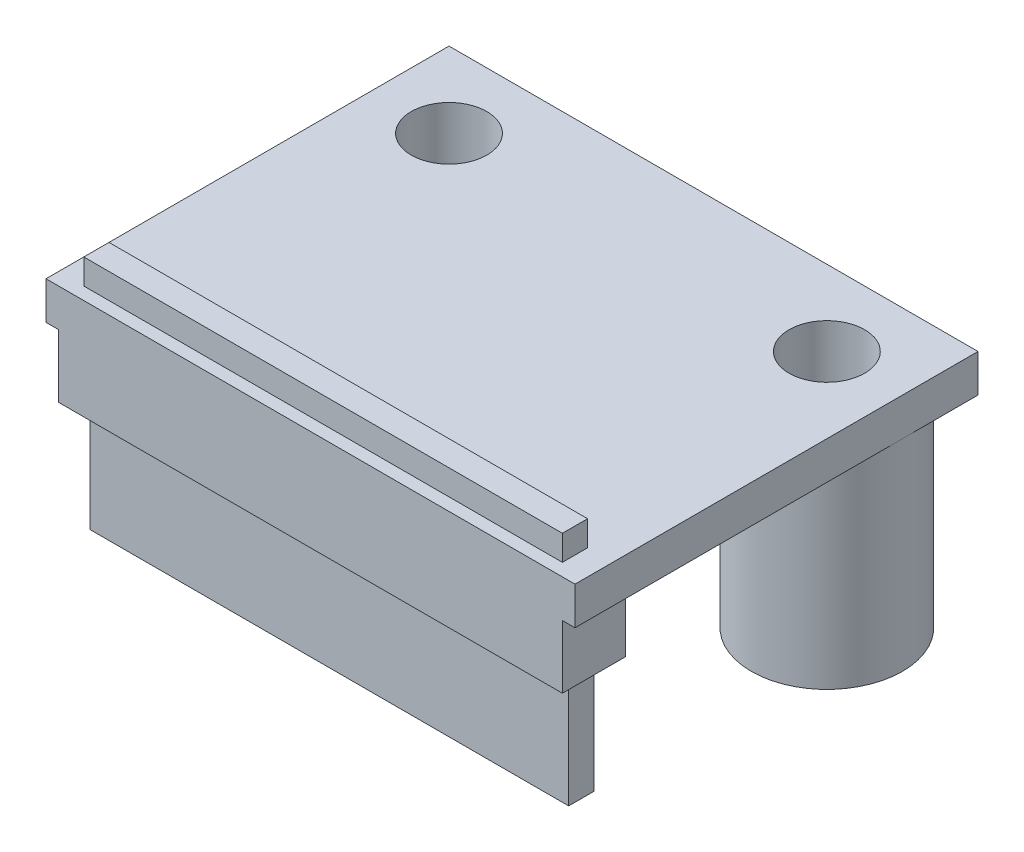
SolidWorks part; units mm, degrees
ref_plane "Front" through (0, 0, 0) normal (0, 0, 1) x (1, 0, 0)
ref_plane "Top" through (0, 0, 0) normal (0, 1, 0) x (1, 0, 0)
ref_plane "Right" through (0, 0, 0) normal (1, 0, 0) x (0, 0, -1)
sketch "Эскиз1" plane through (0, 0, 0) normal (0, 1, 0) x (1, 0, 0)
  line L0 (0, -8) -> (0, 8) construction
  line L1 (-10.5, 8) -> (10.5, 8)
  line L2 (-10.5, 8) -> (-10.5, -8)
  line L3 (-10.5, -8) -> (10.5, -8)
  line L4 (10.5, 8) -> (10.5, -8)
  line L5 (-10.5, 8) -> (10.5, -8) construction
  line L6 (-10.5, -8) -> (10.5, 8) construction
  line L8 (-9.5, -6.5) -> (9.5, -6.5)
  line L9 (-9.5, -6.5) -> (-9.5, -7.5)
  line L10 (-9.5, -7.5) -> (9.5, -7.5)
  line L11 (9.5, -6.5) -> (9.5, -7.5)
  line L12 (-9.5, -6.5) -> (9.5, -7.5) construction
  line L13 (-9.5, -7.5) -> (9.5, -6.5) construction
  circle A0 centre (-7.5, 5) radius 1.5
  circle A1 centre (7.5, 5) radius 1.5
  point P0 (0, 0)
  point P12 (0, -7)
  dimension "D3" = 3
  dimension "D1" = 21
  dimension "D2" = 16
  dimension "D4" = 3
  dimension "D5" = 3
  dimension "D6" = 19
  dimension "D7" = 1
  dimension "D8" = 0.5
extrude "Бобышка-Вытянуть2" add sketch "Эскиз1" against normal blind 1.5 contours L4 L1 L2 L3 A1 A0 L8 L11 L10 L9 | L8 L11 L10 L9 region at (0, 0, -0.2058)
extrude "Бобышка-Вытянуть3" add sketch "Эскиз1<4>" along normal blind 1 contours L8 L11 L10 L9
sketch "Эскиз1<4>" plane through (0, 0, 0) normal (0, 1, 0) x (1, 0, 0) same geometry as "Эскиз1"
sketch "Эскиз3" plane through (0, -1.5, 0) normal (0, -1, 0) x (1, 0, 0)
  line L0 (0, -8) -> (0, 8) construction
  line L1 (-10.5, -8) -> (10.5, -8) construction
  line L2 (-10.5, 8) -> (10.5, 8) construction
  line L4 (-10, 8) -> (10, 8)
  line L5 (-10, 8) -> (-10, 5.5)
  line L6 (-10, 5.5) -> (10, 5.5)
  line L7 (10, 8) -> (10, 5.5)
  line L8 (-10, 8) -> (10, 5.5) construction
  line L9 (-10, 5.5) -> (10, 8) construction
  line L10 (-9.5, 7.25) -> (9.5, 7.25)
  line L11 (-9.5, 7.25) -> (-9.5, 6.25)
  line L12 (-9.5, 6.25) -> (9.5, 6.25)
  line L13 (9.5, 7.25) -> (9.5, 6.25)
  line L14 (-9.5, 7.25) -> (9.5, 6.25) construction
  line L15 (-9.5, 6.25) -> (9.5, 7.25) construction
  point P6 (0, 6.75)
  point P11 (0, 6.75)
  dimension "D1" = 1
  dimension "D2" = 2.5
  dimension "D3" = 19
  dimension "D4" = 20
extrude "Бобышка-Вытянуть4" add sketch "Эскиз3" along normal blind 7 contours L13 L10 L11 L12 region at (0, -1.5, 6.75)
extrude "Бобышка-Вытянуть5" add sketch "Эскиз3<3>" along normal blind 2.5 contours L6 L7 L4 L5
sketch "Эскиз3<3>" plane through (0, -1.5, 0) normal (0, -1, 0) x (1, 0, 0) same geometry as "Эскиз3"
sketch "Эскиз4" plane through (0, -1.5, 0) normal (0, -1, 0) x (1, 0, 0)
  circle A0 centre (-7.5, -5) radius 3
  circle A1 centre (7.5, -5) radius 3
  circle M1 centre (-7.5, -5) radius 1.5
  circle M2 centre (7.5, -5) radius 1.5
  dimension "D1" = 6
extrude "Бобышка-Вытянуть6" add sketch "Эскиз4" along normal blind 8 contours A0 M1 | A1 M2 region at (-10.4151, -1.5, -5) region at (4.5849, -1.5, -5)
